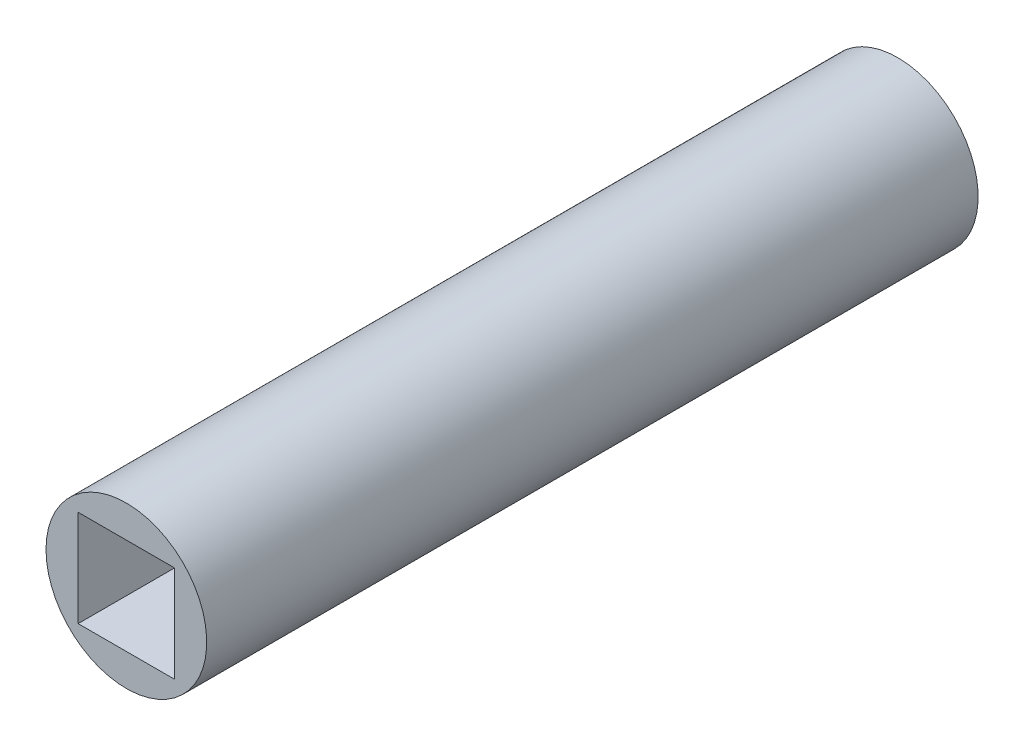
SolidWorks part; units mm, degrees
material "PLA"
ref_plane "Front Plane" through (0, 0, 0) normal (0, 0, 1) x (1, 0, 0)
ref_plane "Top Plane" through (0, 0, 0) normal (0, 1, 0) x (1, 0, 0)
ref_plane "Right Plane" through (0, 0, 0) normal (1, 0, 0) x (0, 0, -1)
sketch "Sketch1" plane through (0, 0, 0) normal (0, 1, 0) x (1, 0, 0)
  line L1 (0, 0) -> (-15.875, 0)
  line L2 (0, 0) -> (0, -152.4)
  line L3 (0, -152.4) -> (-15.875, -152.4)
  line L4 (-15.875, 0) -> (-15.875, -152.4)
  dimension "D1" = 152.4
  dimension "D2" = 15.875
revolve "Revolve1" add sketch "Sketch1" angle 360 about L2
sketch "Sketch2" plane through (0, 0, 152.4) normal (0, 0, 1) x (1, 0, 0)
  line L1 (-9.525, 9.525) -> (9.525, 9.525)
  line L2 (-9.525, 9.525) -> (-9.525, -9.525)
  line L3 (-9.525, -9.525) -> (9.525, -9.525)
  line L4 (9.525, 9.525) -> (9.525, -9.525)
  line L5 (-9.525, 9.525) -> (9.525, -9.525) construction
  line L6 (-9.525, -9.525) -> (9.525, 9.525) construction
  point P0 (0, 0)
  dimension "D1" = 19.05
  dimension "D2" = 19.05
extrude "Cut-Extrude1" cut sketch "Sketch2" against normal through all contours L2 L1 L4 L3
